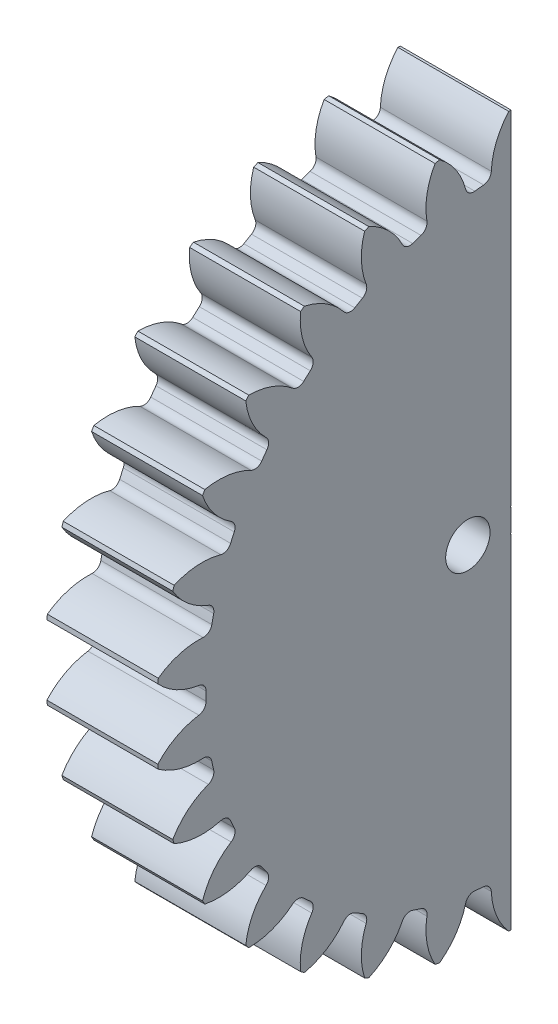
SolidWorks part; units mm, degrees
ref_plane "Front Plane" through (0, 0, 0) normal (1, 0, 0) x (0, 1, 0)
ref_plane "Top Plane" through (0, 0, 0) normal (0, 0, 1) x (0, 1, 0)
ref_plane "Right Plane" through (0, 0, 0) normal (0, 1, 0) x (-1, 0, 0)
sketch "Sketch1" plane through (0, 0, 0) normal (1, 0, 0) x (0, 1, 0)
  circle A0 centre (0, 0) radius 32
  dimension "D1" = 64
extrude "Boss-Extrude1" add sketch "Sketch1" along normal blind 10
sketch "Sketch2" plane through (10, 0, 0) normal (1, 0, 0) x (0, 1, 0)
  line L0 (0, 0) -> (0, 32) construction
  line L1 (0, 0) -> (-1.0999, 27.478) construction
  line L2 (0, 26.2641) -> (3.2427, 19.3101) construction
  arc A0 (1.0999, 27.478) -> (-1.0999, 27.478) centre (0, 0) ccw
  arc A1 (1.7199, 29.9507) -> (-1.7199, 29.9507) centre (0, 0) ccw construction
  arc A2 (3.1367, 31.8459) -> (-3.1367, 31.8459) centre (0, 0) ccw
  arc A3 (-1.0999, 27.478) -> (-3.1367, 31.8459) centre (-7.3373, 27.2283) ccw
  arc A4 (1.0999, 27.478) -> (3.1367, 31.8459) centre (7.3373, 27.2283) cw
  circle A5 centre (0, 0) radius 32 construction
  point P14 (-1.6798, 29.8664)
  dimension "D1" = 64
  dimension "D2" = 60
  dimension "D3" = 4.5
  dimension "D4" = 25
  dimension "D5" = 3.4416
extrude "Cut-Extrude1" cut sketch "Sketch2" against normal through all
fillet "Fillet1" radius 0.76 2 edges at (5, 1.0999, 27.478) (5, -1.0999, 27.478)
pattern_circular "CirPattern1" count 30 over 360 about axis through (10, 0, 0) along (1, 0, 0) of "Cut-Extrude1", "Fillet1"
sketch "Sketch3" plane through (10, 0, 0) normal (1, 0, 0) x (0, 1, 0)
  line L0 (2, -1.5) -> (2, 1.5)
  arc A0 (2, 1.5) -> (2, -1.5) centre (0, 0) ccw
  dimension "D1" = 2.5
  dimension "D2" = 2
extrude "Cut-Extrude2" [suppressed] cut sketch "Sketch3" against normal through all
sketch "Sketch4" plane through (10, 0, 0) normal (1, 0, 0) x (0, 1, 0)
  line L0 (-32, 0) -> (32, 0)
  circle A0 centre (0, 0) radius 32 construction
  arc A1 (-32, 0) -> (32, 0) centre (0, 0) ccw
  point P7 (0, 0)
extrude "Cut-Extrude3" cut sketch "Sketch4" against normal through all
ref_plane "Plane1" through (0, 0, 2) normal (0, 0, -1) x (-1, 0, 0)
sketch "Sketch8" plane through (0, 0, 2) normal (0, 0, -1) x (-1, 0, 0)
  line L0 (-5, 32) -> (-5, -32) construction
  line L1 (0, 32) -> (-10, 32) construction
  line L2 (0, -32) -> (-10, -32) construction
  line L3 (0, 0) -> (-10, 0) construction
  line L4 (-3.3546, 5.15) -> (-1.7091, 8)
  line L5 (-1.7091, 8) -> (-3.3546, 10.85)
  line L6 (-3.3546, 10.85) -> (-6.6454, 10.85)
  line L7 (-6.6454, 10.85) -> (-8.2909, 8) construction
  line L8 (-8.2909, 8) -> (-6.6454, 5.15) construction
  line L9 (-6.6454, 5.15) -> (-3.3546, 5.15)
  line L10 (-10, 32) -> (-10, -32) construction
  line L11 (-6.6454, 5.15) -> (-10, 5.15)
  line L12 (-10, 5.15) -> (-10, 10.85)
  line L13 (-10, 10.85) -> (-6.6454, 10.85)
  line L14 (-8.2909, -8) -> (-6.6454, -5.15) construction
  line L15 (-6.6454, -10.85) -> (-8.2909, -8) construction
  line L16 (-10, -10.85) -> (-6.6454, -10.85)
  line L17 (-10, -5.15) -> (-10, -10.85)
  line L18 (-6.6454, -5.15) -> (-10, -5.15)
  line L19 (-6.6454, -5.15) -> (-3.3546, -5.15)
  line L20 (-3.3546, -10.85) -> (-6.6454, -10.85)
  line L21 (-1.7091, -8) -> (-3.3546, -10.85)
  line L22 (-3.3546, -5.15) -> (-1.7091, -8)
  circle A0 centre (-5, 8) radius 2.85 construction
  circle A1 centre (-5, -8) radius 2.85 construction
  dimension "D1" = 5.7
  dimension "D2" = 16
extrude "Cut-Extrude6" [suppressed] cut sketch "Sketch8" against normal blind 2.6
sketch "Sketch9" [suppressed] plane through (0, 0, 0) normal (0, 0, -1) x (1, 0, 0)
  line L0 (5, 32) -> (5, -32) construction
  line L1 (0, 32) -> (10, 32) construction
  line L2 (0, -32) -> (10, -32) construction
  line L3 (0, 0) -> (10, 0) construction
  line L4 (10, -32) -> (10, 32) construction
  line L5 (1.7091, 8) -> (3.3546, 5.15)
  line L6 (3.3546, 10.85) -> (1.7091, 8)
  line L7 (10, 10.85) -> (3.3546, 10.85)
  line L8 (10, 5.15) -> (10, 10.85)
  line L9 (3.3546, 5.15) -> (10, 5.15)
  line L10 (1.7091, 8) -> (3.3546, 5.15) construction
  line L11 (3.3546, 10.85) -> (1.7091, 8) construction
  line L12 (10, 10.85) -> (3.3546, 10.85) construction
  line L13 (10, 5.15) -> (10, 10.85) construction
  line L14 (3.3546, 5.15) -> (10, 5.15) construction
  line L15 (3.3546, -5.15) -> (10, -5.15) construction
  line L16 (10, -5.15) -> (10, -10.85) construction
  line L17 (10, -10.85) -> (3.3546, -10.85) construction
  line L18 (3.3546, -10.85) -> (1.7091, -8) construction
  line L19 (1.7091, -8) -> (3.3546, -5.15) construction
  circle A0 centre (5, 8) radius 1.75
  circle A1 centre (5, -8) radius 1.75
  dimension "D2" = 3.5
  dimension "D1" = 0
extrude "Cut-Extrude7" [suppressed] cut sketch "Sketch9" against normal blind 11
sketch "Sketch12" [suppressed] plane through (10, 0, 0) normal (1, 0, 0) x (0, 1, 0)
  circle A0 centre (0, 0) radius 10.5
  dimension "D1" = 21
extrude "Cut-Extrude8" [suppressed] cut sketch "Sketch12" against normal through all and the other way through all
sketch "Sketch17" [suppressed] plane through (0, 0, 0) normal (-1, 0, 0) x (0, -1, 0)
  circle A0 centre (0, 0) radius 8
  circle A2 centre (0, 0) radius 12.7
  dimension "D1" = 25.4
extrude "Boss-Extrude3" [suppressed] add sketch "Sketch17" along normal blind 1
sketch "Sketch22" [suppressed] plane through (0, 0, 0) normal (-1, 0, 0) x (0, -1, 0)
  circle A0 centre (0, 0) radius 27.5
  circle A1 centre (0, 0) radius 10.5 construction
  circle A2 centre (0, 0) radius 10.5
  arc A3 (-6.1081, -26.8131) -> (-5.3258, -26.9794) centre (0, 0) ccw construction
extrude "Boss-Extrude6" [suppressed] add sketch "Sketch22" along normal blind 2
sketch "Sketch28" [suppressed] plane through (10, 0, 0) normal (1, 0, 0) x (0, 1, 0)
  line L0 (-10.5, 0) -> (10.5, 0) construction
  line L1 (-10.4523, -1) -> (10.4523, -1)
  line L2 (-10.5, -2) -> (10.5, -2) construction
  line L3 (-10.3078, -2) -> (10.3078, -2)
  line L4 (-10.5, -1) -> (10.5, -1) construction
  line L5 (-10.3078, 2) -> (10.3078, 2)
  line L6 (-10.4523, 1) -> (10.4523, 1)
  circle A0 centre (0, 0) radius 10.5 construction
  arc A1 (-10.4523, -1) -> (-10.3078, -2) centre (0, 0) ccw
  arc A2 (10.3078, -2) -> (10.4523, -1) centre (0, 0) ccw
  arc A3 (-10.4523, 1) -> (-10.3078, 2) centre (0, 0) cw
  arc A4 (10.3078, 2) -> (10.4523, 1) centre (0, 0) cw
  dimension "D1" = 1
  dimension "D3" = 1
extrude "Boss-Extrude7" [suppressed] add sketch "Sketch28" against normal up to surface (12 mm away) up to face at (10, 0, 18.2013)
sketch "Sketch29" [suppressed] plane through (-2, 0, 0) normal (-1, 0, 0) x (0, -1, 0)
  line L1 (-15, -15) -> (15, -15)
  line L2 (-15, -15) -> (-15, 15)
  line L3 (-15, 15) -> (15, 15)
  line L4 (15, -15) -> (15, 15)
  line L5 (-15, -15) -> (15, 15) construction
  line L6 (-15, 15) -> (15, -15) construction
  circle A1 centre (0, 0) radius 10.5
  point P0 (0, 0)
  dimension "D1" = 30
extrude "Boss-Extrude8" [suppressed] add sketch "Sketch29" along normal blind 4
sketch "Sketch30" [suppressed] plane through (0, 0, 0) normal (0, 0, 1) x (0, 1, 0)
  line L0 (15, 2) -> (17.5, 4.5)
  line L1 (17.5, 4.5) -> (17.5, 12.05)
  line L2 (17.5, 12.05) -> (14.5, 9.05)
  line L3 (14.5, 9.05) -> (14.5, 8.3)
  line L4 (14.5, 8.3) -> (15.5, 8.3)
  line L5 (15.5, 8.3) -> (15.5, 5.75)
  line L6 (15.5, 5.75) -> (15, 5.75)
  line L7 (15, 6) -> (15, 2) construction
  line L8 (15, 5.75) -> (15, 2)
  line L9 (-15, 6) -> (15, 6) construction
  line L10 (27.5, 2) -> (-27.5, 2) construction
  dimension "D1" = 0.25
  dimension "D2" = 0.5
  dimension "D3" = 1
  dimension "D4" = 3
  dimension "D5" = 45
  dimension "D6" = 0.75
  dimension "D7" = 2.3
  dimension "D8" = 45
extrude "Boss-Extrude9" [suppressed] add sketch "Sketch30" along normal blind 5 and the other way blind 5
sketch "Sketch31" [suppressed] plane through (0, 17.5, 0) normal (0, 1, 0) x (-1, 0, 0)
  line L0 (6, 5) -> (12.05, 4)
  line L1 (4.5, 5) -> (12.05, 5) construction
  line L2 (6, 15) -> (6, -15) construction
  line L3 (12.05, -5) -> (12.05, 5) construction
  line L4 (12.05, 4) -> (12.05, 5)
  line L5 (12.05, 5) -> (6, 5)
  line L6 (12.05, 0) -> (4.5, 0) construction
  line L7 (4.5, -5) -> (4.5, 5) construction
  line L8 (12.05, -4) -> (12.05, -5)
  line L9 (6, -5) -> (12.05, -4)
  line L10 (12.05, -5) -> (6, -5)
  dimension "D1" = 8
extrude "Cut-Extrude9" [suppressed] cut sketch "Sketch31" against normal up to next
ref_plane "Plane2" [suppressed] through (0, 0, 0) normal (0, 0.7071, -0.7071) x (0, 0.7071, 0.7071)
mirror "Mirror1" [suppressed] about plane through (0, 0, 0) normal (0, 1, 0)
mirror "Mirror2" [suppressed] about plane through (0, 0, 0) normal (0, 0.7071, -0.7071)
sketch "Sketch32" plane through (10, 0, 0) normal (1, 0, 0) x (0, 1, 0)
  line L0 (0, 0) -> (0, -0.5297) construction
  line L1 (32, 0) -> (-32, 0) construction
  line L2 (1, 0.05) -> (1.1, 0.05)
  line L3 (-1, 0) -> (-1.1, 0)
  line L4 (-1, 0) -> (-1, 0.05)
  line L5 (-1, 0.05) -> (-1.1, 0.05)
  line L6 (-1.1, 0) -> (-1.1, 0.05)
  line L7 (1.1, 0) -> (1.1, 0.05)
  line L8 (1, 0) -> (1.1, 0)
  line L9 (1, 0) -> (1, 0.05)
  dimension "D1" = 0.1
  dimension "D2" = 0.05
  dimension "D3" = 1
extrude "Cut-Extrude10" cut sketch "Sketch32" against normal through all both and the other way through all
sketch "Sketch34" plane through (10, 0, 0) normal (1, 0, 0) x (0, 0, -1)
  circle A0 centre (-3.9, 0) radius 2 construction
  circle A1 centre (-3.9, 0) radius 2
extrude "Cut-Extrude12" cut sketch "Sketch34" against normal through all both and the other way through all
equation "\"No. of Teeth\"= 30"
equation "\"Module\"= 2"
equation "\"Bore Diameter\"= 5"
equation "\"Pressure Angle\"= 25"
equation "\"Outer Diameter\"= ( \"No. of Teeth\" + 2 ) * \"Module\""
equation "\"Pitch Diameter\"= ( \"No. of Teeth\" * \"Module\" )"
equation "\"Backlash\"= 0.15 * \"Module\""
equation "\"Arc Length\"= ( ( \"Module\" * pi ) / 2 ) + \"Backlash\""
equation "\"Filet Radius\"= 0.38 * \"Module\""
equation "\"Tooth Depth\"= IIF ( \"Module\" <= 1.25 , \"Module\" * 2.4 , \"Module\" * 2.25 )"
equation "\"D1@Fillet1\"=\"Filet Radius\""
equation "\"D1@CirPattern1\"=\"No. of Teeth\""
equation "\"D1@Sketch1\"=\"Outer Diameter\""
equation "\"D5@Sketch2\"=\"Arc Length\""
equation "\"D4@Sketch2\"=\"Pressure Angle\""
equation "\"D2@Sketch2\"=\"Pitch Diameter\""
equation "\"D1@Sketch2\"=\"Outer Diameter\""
equation "\"D3@Sketch2\"= \"Tooth Depth\""
